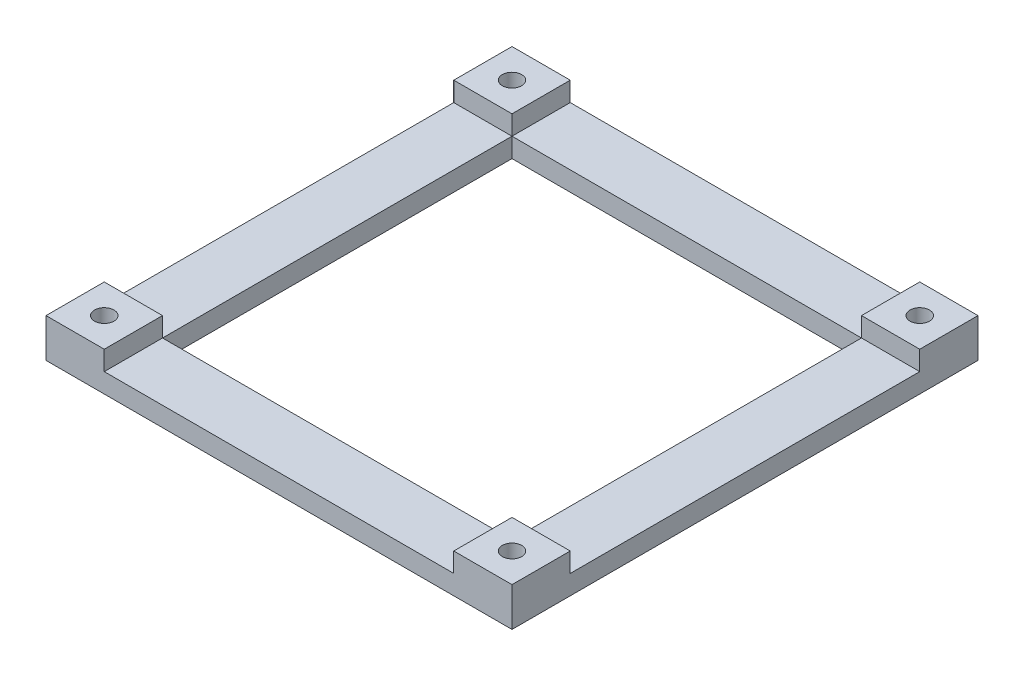
SolidWorks part; units mm, degrees
ref_plane "Front Plane" through (0, 0, 0) normal (0, 0, 1) x (1, 0, 0)
ref_plane "Top Plane" through (0, 0, 0) normal (0, 1, 0) x (1, 0, 0)
ref_plane "Right Plane" through (0, 0, 0) normal (1, 0, 0) x (0, 0, -1)
sketch "Sketch2" plane through (0, 0, 0) normal (0, 1, 0) x (1, 0, 0)
  line L0 (-45, 45) -> (45, 45)
  line L1 (-60, -60) -> (60, -60)
  line L2 (-60, -60) -> (-60, 60)
  line L3 (-60, 60) -> (60, 60)
  line L4 (60, -60) -> (60, 60)
  line L5 (-60, -60) -> (60, 60) construction
  line L6 (-60, 60) -> (60, -60) construction
  line L7 (45, -45) -> (45, 45)
  line L8 (-45, -45) -> (45, -45)
  line L9 (-45, -45) -> (-45, 45)
  point P0 (0, 0)
  dimension "D1" = 120
  dimension "D2" = 120
  dimension "D3" = 15
extrude "Boss-Extrude1" add sketch "Sketch2" along normal blind 5
sketch "Sketch3" plane through (0, 5, 0) normal (0, 1, 0) x (1, 0, 0)
  line L0 (45, 45) -> (45, 60)
  line L1 (-45, 45) -> (-60, 45)
  line L2 (-45, 45) -> (-45, 60)
  line L3 (-45, 60) -> (-60, 60)
  line L4 (-60, 45) -> (-60, 60)
  line L5 (45, 60) -> (60, 60)
  line L6 (45, 45) -> (60, 45)
  line L7 (60, 45) -> (60, 60)
  line L8 (45, -45) -> (60, -45)
  line L9 (60, -45) -> (60, -60)
  line L10 (45, -45) -> (45, -60)
  line L11 (45, -60) -> (60, -60)
  line L12 (-45, -45) -> (-45, -60)
  line L13 (-45, -60) -> (-60, -60)
  line L14 (-45, -45) -> (-60, -45)
  line L15 (-60, -45) -> (-60, -60)
  line L16 (-60, 60) -> (60, -60) construction
  line L17 (60, 60) -> (-60, -60) construction
  point P6 (0, 0)
  point P7 (60, 52.5)
  point P21 (0, 0)
  dimension "D2" = 90
  dimension "D1" = 4
extrude "Boss-Extrude2" add sketch "Sketch3" along normal blind 5
sketch "Sketch4" plane through (0, 10, 0) normal (0, 1, 0) x (1, 0, 0)
  line L0 (-60, -45) -> (-45, -60) construction
  line L1 (-45, -45) -> (-60, -60) construction
  line L2 (-60, -60) -> (60, 60) construction
  line L3 (-60, 60) -> (60, -60) construction
  circle A0 centre (-52.5, -52.5) radius 2.5
  circle A1 centre (-52.5, 52.5) radius 2.5
  circle A2 centre (52.5, 52.5) radius 2.5
  circle A3 centre (52.5, -52.5) radius 2.5
  point P19 (0, 0)
  point P23 (0, 0)
  point P24 (0, 0)
  dimension "D1" = 5
  dimension "D2" = 4
extrude "Cut-Extrude1" cut sketch "Sketch4" against normal through all
